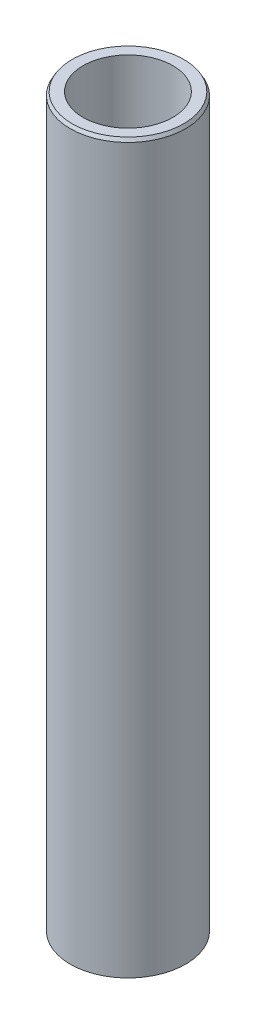
SolidWorks part; units mm, degrees
ref_plane "Front Plane" through (0, 0, 0) normal (0, 0, 1) x (1, 0, 0)
ref_plane "Top Plane" through (0, 0, 0) normal (0, 1, 0) x (1, 0, 0)
ref_plane "Right Plane" through (0, 0, 0) normal (1, 0, 0) x (0, 0, -1)
sketch "Sketch1" plane through (0, 0, 0) normal (0, 1, 0) x (1, 0, 0)
  circle A0 centre (0, 0) radius 47.5
  dimension "SHAFT_OD" = 95
extrude "Boss-Extrude1" add sketch "Sketch1" along normal blind 600
sketch "Sketch2" plane through (0, 0, 0) normal (0, 1, 0) x (1, 0, 0)
  circle A0 centre (0, 0) radius 36.9484
  dimension "BORE_D" = 73.8968
extrude "Cut-Extrude1" cut sketch "Sketch2" along normal through all
chamfer "Chamfer1" distance 2.7455 angle 30 2 edges at (0, 600, 47.5) (0, 0, 47.5) first distance on face at (0, 600, 47.5) first distance on face at (0, 0, 36.9484)
